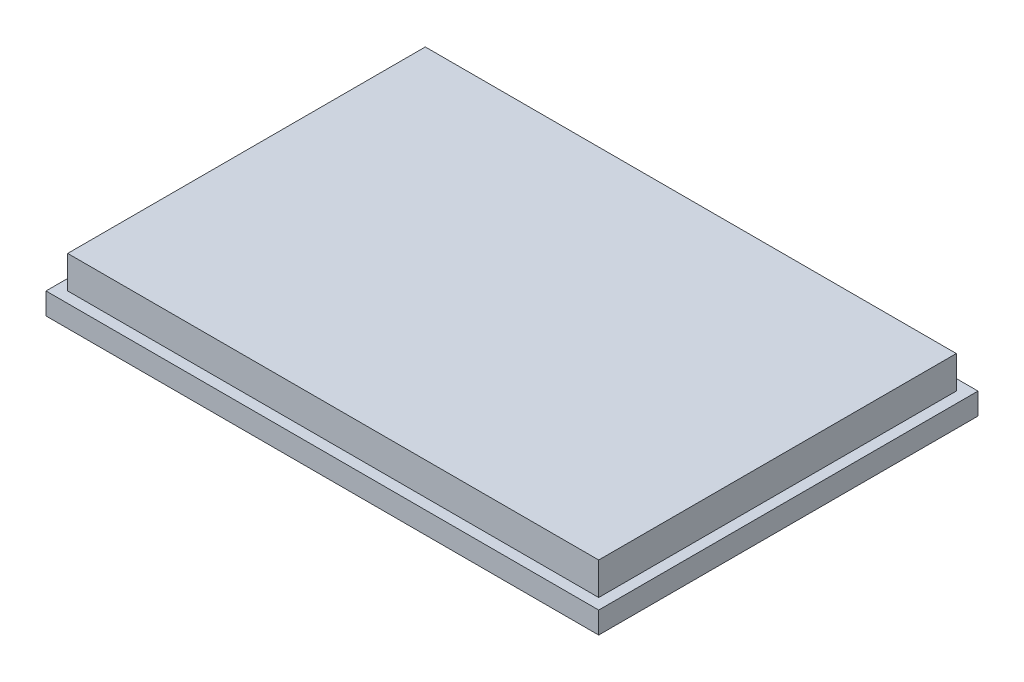
SolidWorks part; units mm, degrees
ref_plane "Front Plane" through (0, 0, 0) normal (0, 0, 1) x (1, 0, 0)
ref_plane "Top Plane" through (0, 0, 0) normal (0, 1, 0) x (1, 0, 0)
ref_plane "Right Plane" through (0, 0, 0) normal (1, 0, 0) x (0, 0, -1)
sketch "Sketch1" plane through (0, 0, 0) normal (0, 1, 0) x (1, 0, 0)
  line L1 (0, 0) -> (51, 0)
  line L2 (0, 0) -> (0, -35)
  line L3 (0, -35) -> (51, -35)
  line L4 (51, 0) -> (51, -35)
  dimension "D1" = 51
  dimension "D2" = 35
extrude "Boss-Extrude1" add sketch "Sketch1" along normal blind 2
sketch "Sketch2" plane through (0, 2, 0) normal (0, 1, 0) x (1, 0, 0)
  line L0 (51, 0) -> (0, 0) construction
  line L1 (1, -1) -> (50, -1)
  line L2 (1, -1) -> (1, -34)
  line L3 (1, -34) -> (50, -34)
  line L4 (50, -1) -> (50, -34)
  line L5 (0, 0) -> (0, -35) construction
  dimension "D1" = 49
  dimension "D2" = 33
  dimension "D3" = 1
  dimension "D4" = 1
extrude "Boss-Extrude2" add sketch "Sketch2" along normal blind 3
sketch "Sketch3" plane through (0, 0, 0) normal (0, -1, 0) x (1, 0, 0)
  line L0 (0, 35) -> (51, 35) construction
  line L1 (25.0892, 20) -> (30.5804, 20)
  line L2 (25.0892, 20) -> (25.0892, 17)
  line L3 (25.0892, 17) -> (30.5804, 17)
  line L4 (30.5804, 20) -> (30.5804, 17)
  dimension "D1" = 15
  dimension "D2" = 3
extrude "Boss-Extrude3" add sketch "Sketch3" along normal blind 5
sketch "Sketch4" plane through (0, 0, 20) normal (0, 0, 1) x (1, 0, 0)
  circle A0 centre (27.5602, -2.6198) radius 1
  dimension "D1" = 2
extrude "Cut-Extrude1" cut sketch "Sketch4" against normal through all
